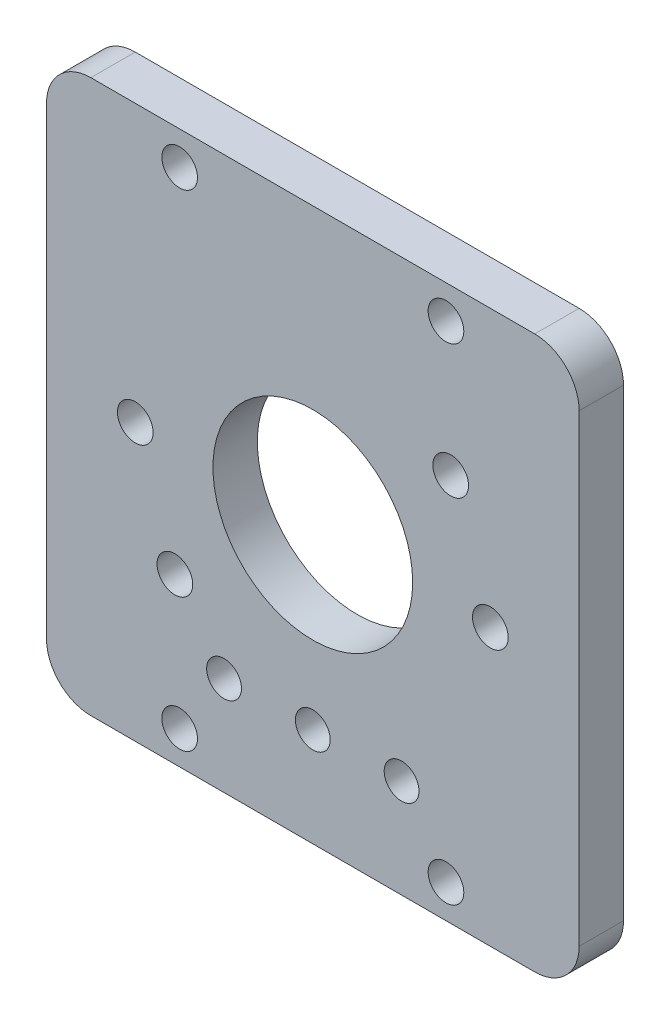
SolidWorks part; units mm, degrees
material "6061-T6 (SS)"
ref_plane "Front Plane" through (0, 0, 0) normal (0, 0, 1) x (1, 0, 0)
ref_plane "Top Plane" through (0, 0, 0) normal (0, 1, 0) x (1, 0, 0)
ref_plane "Right Plane" through (0, 0, 0) normal (1, 0, 0) x (0, 0, -1)
sketch "Sketch5" plane through (0, 0, 0) normal (0, 0, 1) x (1, 0, 0)
  line L0 (-19.7318, -15.9943) -> (19.7318, 15.9943) construction
  line L1 (0, 0) -> (25.4, 0) construction
  line L2 (-19.05, 34.7624) -> (19.05, 34.7624) construction
  line L3 (-38.1, -39.5249) -> (38.1, -39.5249)
  line L4 (-38.1, -39.5249) -> (-38.1, 39.5249)
  line L5 (-38.1, 39.5249) -> (38.1, 39.5249)
  line L6 (38.1, -39.5249) -> (38.1, 39.5249)
  line L7 (-38.1, -39.5249) -> (38.1, 39.5249) construction
  line L8 (-38.1, 39.5249) -> (38.1, -39.5249) construction
  line L9 (-38.1, 0) -> (38.1, 0) construction
  line L10 (-19.05, -34.7624) -> (19.05, -34.7624) construction
  line L11 (-12.7, -25.4) -> (12.7, -25.4) construction
  line L12 (25.4, -39.5249) -> (-29.5586, -39.5249)
  line L16 (-38.1, -12.7) -> (38.1, -12.7) construction
  line L17 (-38.1, -12.7) -> (-38.1, 12.7) construction
  line L18 (-38.1, 12.7) -> (38.1, 12.7) construction
  line L19 (38.1, -12.7) -> (38.1, 12.7) construction
  line L20 (-38.1, -12.7) -> (38.1, 12.7) construction
  line L21 (-38.1, 12.7) -> (38.1, -12.7) construction
  circle A0 centre (0, 0) radius 14.2875
  circle A1 centre (0, 0) radius 25.4 construction
  circle A2 centre (-19.7318, -15.9943) radius 2.5527
  circle A3 centre (19.7318, 15.9943) radius 2.5527
  circle A6 centre (-19.05, 34.7624) radius 2.5527
  circle A7 centre (19.05, 34.7624) radius 2.5527
  circle A8 centre (19.05, -34.7624) radius 2.5527
  circle A9 centre (-19.05, -34.7624) radius 2.5527
  circle A13 centre (-25.4, 0) radius 2.5527
  circle A14 centre (25.4, 0) radius 2.5527
  circle A15 centre (-12.7, -25.4) radius 2.4892
  circle A16 centre (12.7, -25.4) radius 2.4892
  circle A17 centre (0, -25.4) radius 2.4892
  point P8 (0, 0)
  point P19 (0, 34.7624)
  point P37 (0, -25.4)
  dimension "D1" = 28.575
  dimension "D2" = 5.1054
  dimension "D3" = 50.8
  dimension "D5" = 19.05
  dimension "D6" = 5.1054
  dimension "D8" = 76.2
  dimension "D11" = 12.7
  dimension "D12" = 12.7
  dimension "D14" = 5.1054
  dimension "D10" = 4.9784
  dimension "D4" = 34.7624
  dimension "45" = 39.028
  dimension "D7" = 4.7625
  dimension "D9" = 25.4
extrude "Boss-Extrude1" add sketch "Sketch5" along normal blind 6.35 contours L3 L6 L5 L4 A14 A13 A8 A7 A6 A3 A2 A0 A9 | L3 region at (-37.002, 0, 0)
fillet "Fillet2" radius 6.35 4 edges at (-38.1, -39.5249, 3.175) (38.1, -39.5249, 3.175) (38.1, 39.5249, 3.175) (-38.1, 39.5249, 3.175)
equation "\"NEO\"= 60mm"
